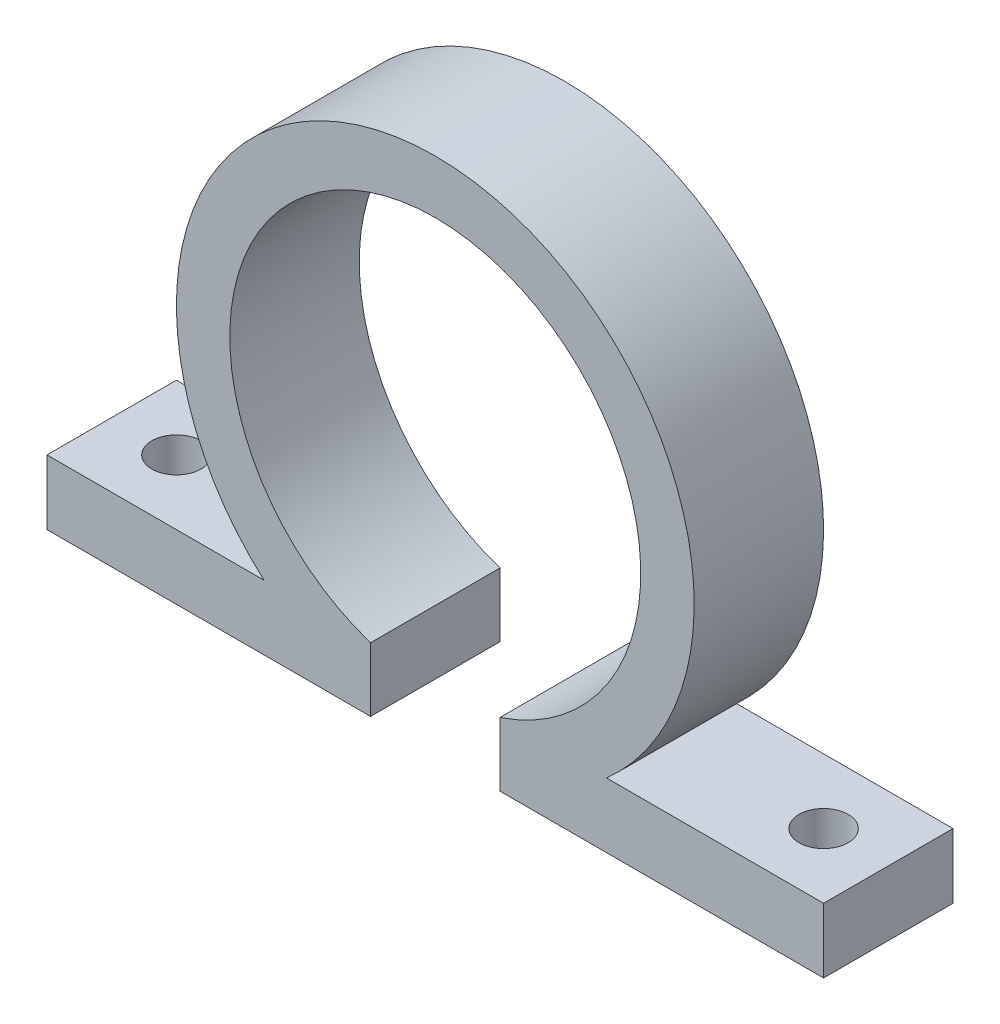
SolidWorks part; units mm, degrees
ref_plane "Front Plane" through (0, 0, 0) normal (0, 0, 1) x (1, 0, 0)
ref_plane "Top Plane" through (0, 0, 0) normal (0, 1, 0) x (1, 0, 0)
ref_plane "Right Plane" through (0, 0, 0) normal (1, 0, 0) x (0, 0, -1)
sketch "Sketch1" plane through (0, 0, 0) normal (0, 0, 1) x (1, 0, 0)
  circle A0 centre (0, 0) radius 20
  dimension "D1" = 40
extrude "Boss-Extrude1" add sketch "Sketch1" along normal blind 10
sketch "Sketch2" plane through (0, 0, 0) normal (0, 0, -1) x (-1, 0, 0)
  line L1 (30, -15) -> (-30, -15)
  line L2 (30, -15) -> (30, -20)
  line L3 (30, -20) -> (-30, -20)
  line L4 (-30, -15) -> (-30, -20)
  circle A0 centre (0, 0) radius 20 construction
  dimension "D2" = 20
  dimension "D1" = 5
  dimension "D3" = 60
  dimension "D4" = 30
extrude "Boss-Extrude2" add sketch "Sketch2" against normal blind 10
sketch "Sketch3" plane through (0, 0, 0) normal (0, 0, -1) x (-1, 0, 0)
  circle A0 centre (0, 0) radius 15.875
  dimension "D1" = 31.75
extrude "Cut-Extrude1" cut sketch "Sketch3" against normal through all
sketch "Sketch4" plane through (0, 0, 10) normal (0, 0, 1) x (1, 0, 0)
  line L0 (30, -20) -> (-30, -20) construction
  line L1 (-5, -15.067) -> (5, -15.067)
  line L2 (-5, -15.067) -> (-5, -20)
  line L3 (-5, -20) -> (5, -20)
  line L4 (5, -15.067) -> (5, -20)
  line L5 (-30, -20) -> (-30, -15) construction
  circle A0 centre (0, 0) radius 15.875 construction
  dimension "D1" = 25
  dimension "D2" = 10
extrude "Cut-Extrude2" cut sketch "Sketch4" against normal through all
hole_wizard "#6 Clearance Hole1" positions "Sketch6" profile "Sketch7" hole size "#6" standard "ANSI Inch" end condition through all
sketch "Sketch6" plane through (0, -15, 0) normal (0, 1, 0) x (1, 0, 0)
  line L0 (-30, 0) -> (-13.2288, 0) construction
  line L1 (-30, -10) -> (-30, 0) construction
  point P0 (-25, -5)
  point P10 (0, 0)
  point P11 (0, 0)
  dimension "D1" = 5
  dimension "D2" = 5
sketch "Sketch7" plane through (-25, -15, 5) normal (1, 0, 0) x (0, 0, 1)
  line L0 (0, 0) -> (0, 5)
  line L1 (0, 5) -> (1.8986, 5)
  line L2 (1.8986, 5) -> (1.8986, 0)
  line L5 (1.8986, 0) -> (0, 0)
  line L11 (0, -6.35) -> (0, 107.95) construction
  dimension "Thru Hole Dia." = 3.7973
  dimension "Thru Hole Depth" = 5
mirror "Mirror1" about plane through (0, 0, 0) normal (1, 0, 0) of "#6 Clearance Hole1"
